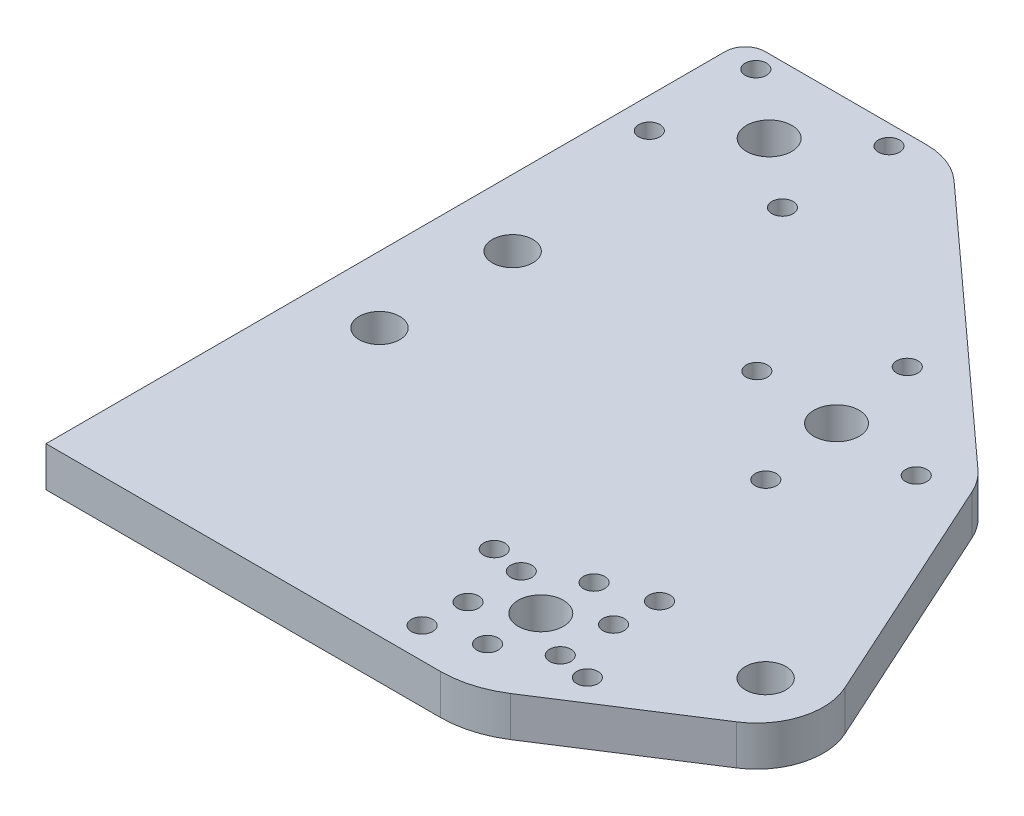
SolidWorks part; units mm, degrees
material "Policarbonato"
ref_plane "Plano frontal" through (0, 0, 0) normal (0, 0, 1) x (1, 0, 0)
ref_plane "Plano superior" through (0, 0, 0) normal (0, 1, 0) x (1, 0, 0)
ref_plane "Plano direito" through (0, 0, 0) normal (1, 0, 0) x (0, 0, -1)
ref_plane "Plano1" through (0, -6, 0) normal (0, -1, 0) x (1, 0, 0)
sketch "Esboço1" plane through (0, -6, 0) normal (0, -1, 0) x (1, 0, 0)
  line L0 (151.2357, -14.2909) -> (167.1948, 20.7865)
  line L1 (163.5005, 33.3393) -> (142.8288, 46.6294)
  line L2 (134.6661, 49.0269) -> (75.4374, 49.0269)
  line L3 (75.4374, 49.0269) -> (75.4374, -53)
  line L4 (78.4374, -56) -> (102.6847, -56)
  line L5 (109.4101, -53.4005) -> (148.859, -17.5502)
  line L6 (134.1775, -0.3541) -> (144.9383, -12.195) construction
  line L7 (144.9383, -12.195) -> (130.1372, -25.6459) construction
  line L8 (130.1372, -25.6459) -> (119.3765, -13.805) construction
  line L9 (119.3765, -13.805) -> (134.1775, -0.3541) construction
  line L10 (134.1775, -0.3541) -> (130.1372, -25.6459) construction
  line L11 (100.0374, -37) -> (80.0374, -53) construction
  line L12 (127.326, 44.4269) -> (146.5154, 38.7906) construction
  line L13 (146.5154, 38.7906) -> (142.0063, 23.4391) construction
  line L14 (142.0063, 23.4391) -> (122.8169, 29.0754) construction
  line L15 (122.8169, 29.0754) -> (127.326, 44.4269) construction
  line L16 (127.326, 44.4269) -> (142.0063, 23.4391) construction
  line L17 (134.6661, 33.933) -> (138.9199, 48.4151) construction
  circle A0 centre (119.3765, -13.805) radius 1.6
  circle A1 centre (146.5154, 38.7906) radius 1.6
  circle A2 centre (142.0063, 23.4391) radius 1.6
  circle A3 centre (159.9953, 25.4877) radius 3.05
  circle A4 centre (100.0374, -37) radius 1.6
  circle A5 centre (100.0374, -53) radius 1.6
  circle A6 centre (80.0374, -37) radius 1.6
  circle A7 centre (80.0374, -53) radius 1.6
  circle A8 centre (122.8169, 29.0754) radius 1.6
  circle A9 centre (127.326, 44.4269) radius 1.6
  circle A10 centre (130.1372, -25.6459) radius 1.6
  circle A11 centre (144.9383, -12.195) radius 1.6
  circle A12 centre (134.1775, -0.3541) radius 1.6
  circle A13 centre (141.5943, 29.933) radius 1.6
  circle A14 centre (134.6661, 25.933) radius 1.6
  circle A15 centre (127.7379, 29.933) radius 1.6
  circle A16 centre (127.7379, 37.933) radius 1.6
  circle A17 centre (134.6661, 41.933) radius 1.6
  circle A18 centre (141.5943, 37.933) radius 1.6
  circle A19 centre (134.6661, 33.933) radius 3.4
  circle A20 centre (132.1574, -13) radius 3.4
  circle A21 centre (90.0374, -45) radius 3.4
  arc A22 (167.1948, 20.7865) -> (163.5005, 33.3393) centre (158.0926, 24.9277) ccw
  arc A23 (142.8288, 46.6294) -> (134.6661, 49.0269) centre (134.6661, 33.933) ccw
  arc A24 (75.4374, -53) -> (78.4374, -56) centre (78.4374, -53) ccw
  arc A25 (102.6847, -56) -> (109.4101, -53.4005) centre (102.6847, -46) ccw
  arc A26 (148.859, -17.5502) -> (151.2357, -14.2909) centre (142.1335, -10.1497) ccw
  point P62 (134.6661, 33.933)
  dimension "D4" = 10
  dimension "D5" = 6.1
  dimension "D8" = 6.8
  dimension "D9" = 3.2
  dimension "D24" = 3
  dimension "D1" = 105.0269
  dimension "D2" = 11
  dimension "D3" = 82.6552
  dimension "D6" = 80.9277
  dimension "D7" = 137.736
  dimension "D10" = 20
  dimension "D11" = 16
  dimension "D12" = 6.6
  dimension "D13" = 52.897
  dimension "D14" = 43
  dimension "D15" = 16
  dimension "D16" = 46.933
  dimension "D17" = 59.2287
  dimension "D18" = 14.6
  dimension "D19" = 8
  dimension "D21" = 26.7
  dimension "D22" = 47.5
  dimension "D23" = 6.6
  dimension "D20" = 6
extrude "Ressalto-extrusão1" add sketch "Esboço1" against normal blind 6
sketch "Esboço2" plane through (0, -6, 0) normal (0, -1, 0) x (1, 0, 0)
  line L0 (75.4374, 49.0269) -> (75.4374, -53) construction
  line L1 (78.428, 16.433) -> (146.9239, 16.433) construction
  circle A0 centre (85.4374, 8.933) radius 3.05
  circle A1 centre (85.4374, -11.067) radius 3.05
  circle A2 centre (85.4374, 8.933) radius 7.5 construction
  circle A3 centre (85.4374, -11.067) radius 7.5 construction
  circle A4 centre (134.6661, 33.933) radius 3.4 construction
  dimension "D1" = 6.1
  dimension "D2" = 15
  dimension "D3" = 20
  dimension "D5" = 25
  dimension "D4" = 10
extrude "Corte-extrusão1" cut sketch "Esboço2" against normal blind 10 contours A1 | A0 region at (85.4374, -6, -11.067)
sketch "Esboço3" plane through (0, -6, 0) normal (0, -1, 0) x (1, 0, 0)
  line L0 (84.7148, -42.8247) -> (118.7445, 40.4401) construction
  line L1 (94.6454, -48.4394) -> (148.4498, 23.6447) construction
  line L2 (84.0455, -40.4974) -> (115.1755, 35.6722) construction
  circle A0 centre (134.6661, 33.933) radius 17.2 construction
  circle A1 centre (90.0374, -45) radius 5.75 construction
  circle A2 centre (85.4374, -11.067) radius 7.5 construction
  circle A3 centre (132.1574, -13) radius 10.75 construction
  dimension "D1" = 34.4
  dimension "D2" = 11.5
  dimension "D3" = 15
  dimension "D4" = 21.5
  dimension "D5" = 1.5
